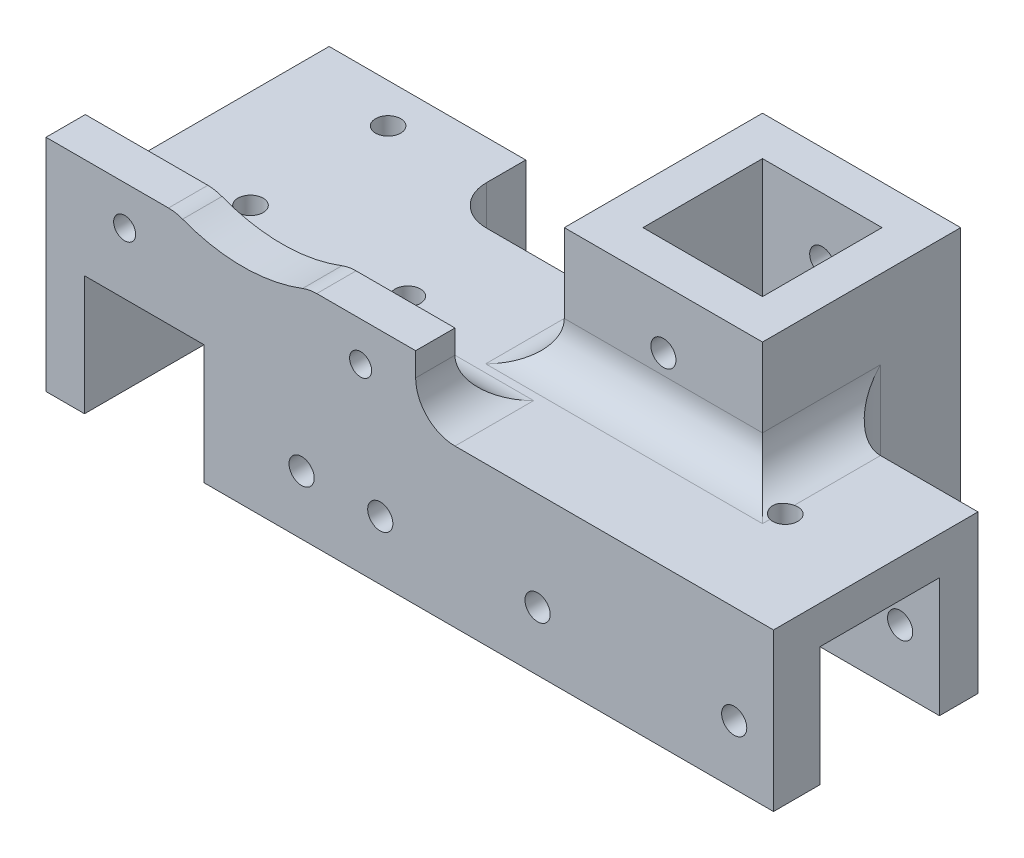
SolidWorks part; units mm, degrees
material "PLA"
ref_plane "前视基准面" through (0, 0, 0) normal (0, 0, 1) x (1, 0, 0)
ref_plane "上视基准面" through (0, 0, 0) normal (0, 1, 0) x (1, 0, 0)
ref_plane "右视基准面" through (0, 0, 0) normal (1, 0, 0) x (0, 0, -1)
sketch "草图1" plane through (0, 0, 0) normal (0, 1, 0) x (1, 0, 0)
  line L0 (-50, 0) -> (30, 0) construction
  line L1 (-50, 7.5) -> (30, 7.5) construction
  line L2 (-50, -7.5) -> (30, -7.5) construction
  line L3 (-37.5, 12.5) -> (-12.6, 12.5)
  line L4 (-7.6, 22.7) -> (7.6, 22.7)
  line L5 (-7.6, 22.7) -> (-7.6, 7.5)
  line L6 (-7.6, 7.5) -> (7.6, 7.5)
  line L7 (7.6, 22.7) -> (7.6, 7.5)
  line L8 (-7.6, 22.7) -> (7.6, 7.5) construction
  line L9 (-7.6, 7.5) -> (7.6, 22.7) construction
  line L10 (-42.5, -27.5) -> (-42.5, 22.5) construction
  line L11 (-30, 0) -> (30, 0) construction
  line L12 (30, 12.5) -> (30, -13.5)
  line L13 (-50, -13.5) -> (-50, 22.5) construction
  line L14 (-12.6, 27.7) -> (-12.6, 12.5)
  line L15 (-12.6, 27.7) -> (12.6, 27.7)
  line L16 (12.6, 27.7) -> (12.6, 12.5)
  line L17 (12.6, 27.7) -> (12.6, 7.5) construction
  line L18 (12.6, 12.5) -> (30, 12.5)
  line L19 (-30, 12.5) -> (30, 12.5) construction
  line L20 (-12.6, 27.7) -> (-12.6, 7.5) construction
  line L21 (-30, 7.5) -> (30, 7.5) construction
  line L22 (-30, -7.5) -> (30, -7.5) construction
  line L23 (-50, -27.5) -> (-50, 22.5) construction
  line L24 (-57.5, -13.5) -> (-57.5, 22.5) construction
  line L25 (-42.5, -13.5) -> (-42.5, 22.5) construction
  line L26 (-37.5, 12.5) -> (-37.5, 22.5)
  line L27 (-37.5, 22.5) -> (-62.5, 22.5)
  line L28 (-62.5, 22.5) -> (-62.5, -13.5)
  line L30 (-57.5, -27.5) -> (-57.5, 22.5) construction
  line L31 (-62.5, -13.5) -> (30, -13.5)
  point P9 (0, 15.1)
  dimension "D3" = 15.2
  dimension "D4" = 30
  dimension "D8" = 50
  dimension "D6" = 6
  dimension "D11" = 15
  dimension "D12" = 5
  dimension "D1" = 7.5
  dimension "D2" = 7.5
  dimension "D5" = 5
  dimension "D7" = 5
  dimension "D9" = 7.5
  dimension "D10" = 7.5
extrude "凸台-拉伸1" add sketch "草图1" along normal blind 20
sketch "草图2" plane through (0, 20, 0) normal (0, 1, 0) x (1, 0, 0)
  line L0 (7.6, 7.5) -> (7.6, 22.7) construction
  line L1 (7.6, 7.5) -> (7.6, 22.7)
  line L2 (-7.6, 7.5) -> (7.6, 7.5) construction
  line L3 (-7.6, 22.7) -> (-7.6, 7.5) construction
  line L4 (7.6, 22.7) -> (-7.6, 22.7) construction
  line L5 (-7.6, 7.5) -> (7.6, 7.5)
  line L6 (-7.6, 22.7) -> (-7.6, 7.5)
  line L7 (7.6, 22.7) -> (-7.6, 22.7)
  line L8 (-12.6, 27.7) -> (-12.6, 2.5)
  line L9 (-12.6, 2.5) -> (12.6, 2.5)
  line L10 (12.6, 2.5) -> (12.6, 27.7)
  line L11 (12.6, 27.7) -> (-12.6, 27.7)
  dimension "D1" = 5
extrude "凸台-拉伸2" add sketch "草图2" along normal blind 15
sketch "草图3" plane through (30, 0, 0) normal (1, 0, 0) x (0, 0, -1)
  line L1 (-7.6, 15.2) -> (7.6, 15.2)
  line L2 (-7.6, 15.2) -> (-7.6, 0)
  line L3 (-7.6, 0) -> (7.6, 0)
  line L4 (7.6, 15.2) -> (7.6, 0)
  line L6 (-13.5, 0) -> (12.5, 0) construction
  point P4 (0, 15.2)
  dimension "D1" = 15.2
extrude "切除-拉伸1" cut sketch "草图3" against normal blind 80
sketch "草图4" plane through (0, 0, 13.5) normal (0, 0, 1) x (1, 0, 0)
  line L0 (-30, 7.5) -> (30, 7.5) construction
  line L1 (-62.5, 0) -> (30, 0) construction
  line L3 (0, 0) -> (0, 7.5) construction
  line L4 (0, 7.5) -> (0, 27.5) construction
  line L5 (-12.6, 35) -> (12.6, 35) construction
  circle A0 centre (0, 7.5) radius 1.6
  circle A1 centre (25, 7.5) radius 1.6
  circle A2 centre (-20, 7.5) radius 1.6
  circle A3 centre (0, 27.5) radius 1.6
  circle A4 centre (-30, 7.5) radius 1.6
  dimension "D1" = 3.2
  dimension "D2" = 25
  dimension "D3" = 3.2
  dimension "D6" = 20
  dimension "D7" = 3.2
  dimension "D8" = 10
  dimension "D4" = 7.5
  dimension "D5" = 7.5
extrude "切除-拉伸2" cut sketch "草图4" against normal through all
fillet "圆角1" radius 5 6 edges at (12.6, 10, -12.5) (-12.6, 10, -12.5) (-12.6, 20, -7.5) (0, 20, -2.5) (12.6, 20, -7.5) (-37.5, 10, -12.5)
sketch "草图5" plane through (0, 0, 13.5) normal (0, 0, 1) x (1, 0, 0)
  line L0 (-62.5, 0) -> (30, 0) construction
  line L1 (-57.6, 0) -> (-42.4, 0)
  line L2 (-57.6, 0) -> (-57.6, 15.2)
  line L3 (-57.6, 15.2) -> (-42.4, 15.2)
  line L4 (-42.4, 0) -> (-42.4, 15.2)
  point P6 (-50, 0)
  dimension "D1" = 50
  dimension "D2" = 15.2
extrude "切除-拉伸3" cut sketch "草图5" against normal through all
sketch "草图7" plane through (0, 20, 0) normal (0, 1, 0) x (1, 0, 0)
  line L0 (0, 0) -> (-50, 0) construction
  line L1 (0, 0) -> (18, 0) construction
  line L2 (-50, 0) -> (-50, 22.5) construction
  line L4 (-37.5, 22.5) -> (-62.5, 22.5) construction
  circle A0 centre (-50, 0) radius 1.6
  circle A1 centre (-30, 0) radius 1.6
  circle A2 centre (18, 0) radius 1.6
  circle A3 centre (-50, 17.5) radius 1.6
  dimension "D2" = 30
  dimension "D3" = 3.2
  dimension "D5" = 5
  dimension "D1" = 50
  dimension "D4" = 18
extrude "切除-拉伸5" cut sketch "草图7" against normal through all both and the other way through all
sketch "草图8" plane through (0, 20, 0) normal (0, 1, 0) x (1, 0, 0)
  line L1 (-62.5, -13.5) -> (-15.5, -13.5)
  line L2 (-62.5, -13.5) -> (-62.5, -8.5)
  line L3 (-62.5, -8.5) -> (-15.5, -8.5)
  line L4 (-15.5, -13.5) -> (-15.5, -8.5)
  dimension "D1" = 5
  dimension "D2" = 47
extrude "凸台-拉伸3" add sketch "草图8" along normal blind 8
sketch "草图9" plane through (0, 0, 13.5) normal (0, 0, 1) x (1, 0, 0)
  line L0 (-37.5, 47.5) -> (-37.5, 0) construction
  line L1 (-42.4, 0) -> (30, 0) construction
  line L2 (-62.5, 28) -> (-62.5, 0) construction
  line L3 (-52.5, 23) -> (-22.5, 23) construction
  line L4 (-62.5, 28) -> (-15.5, 28) construction
  circle A0 centre (-37.5, 47.5) radius 21.25
  circle A1 centre (-52.5, 23) radius 1.4
  circle A2 centre (-22.5, 23) radius 1.4
  point P9 (-37.5, 23)
  dimension "D1" = 42.5
  dimension "D6" = 2.8
  dimension "D2" = 25
  dimension "D3" = 47.5
  dimension "D4" = 30
  dimension "D5" = 5
extrude "切除-拉伸6" cut sketch "草图9" against normal up to next
fillet "圆角2" radius 5 4 edges at (-39, 20, 8.5) (-45.9447, 28, 11) (-29.0553, 28, 11) (-15.5, 20, 11)
